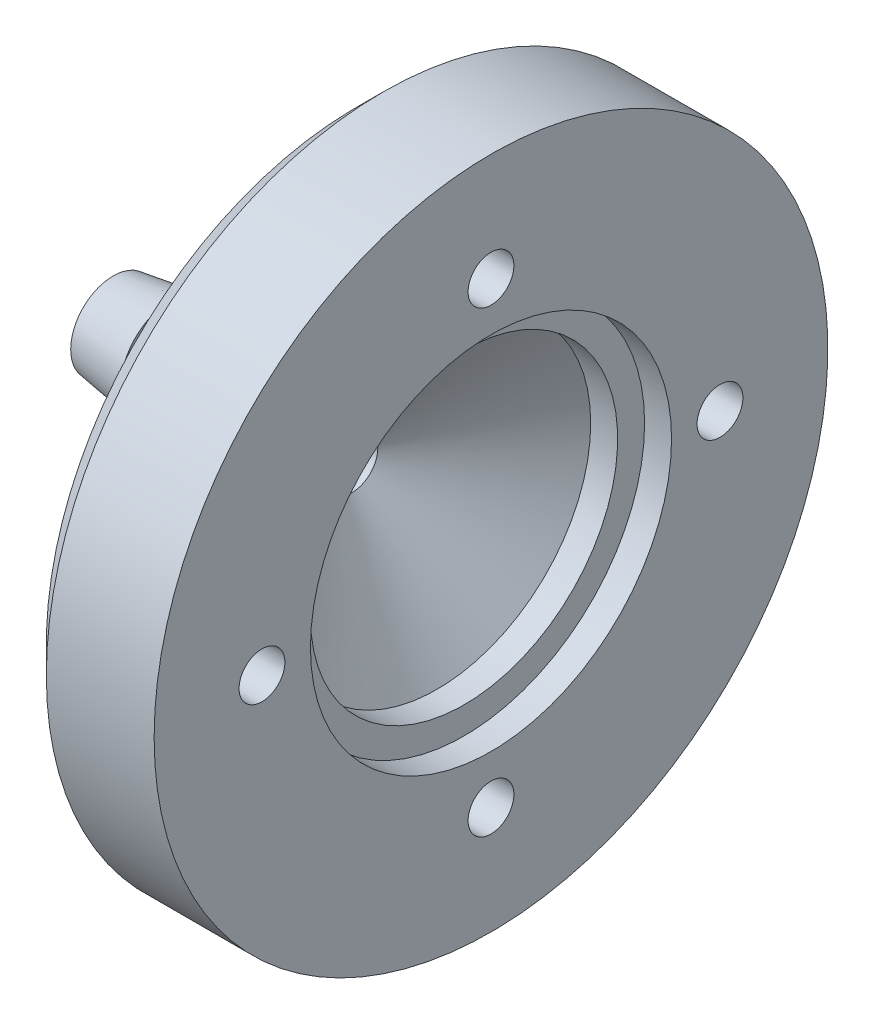
SolidWorks part; units mm, degrees
ref_plane "Front Plane" through (0, 0, 0) normal (0, 0, 1) x (1, 0, 0)
ref_plane "Top Plane" through (0, 0, 0) normal (0, 1, 0) x (1, 0, 0)
ref_plane "Right Plane" through (0, 0, 0) normal (1, 0, 0) x (0, 0, -1)
sketch "Sketch1" plane through (0, 0, 0) normal (0, 0, 1) x (1, 0, 0)
  line L0 (-801.9206, 0) -> (36107.5283, 0) construction
  line L3 (-13.4063, 3.8) -> (-13.4063, 3.15)
  line L8 (-17.7397, 1.9) -> (0, 1.9)
  line L9 (-17.7397, 1.9) -> (-17.7397, 3.15)
  line L10 (10.3016, 13.4) -> (10.3016, 25)
  line L12 (10.3016, 25) -> (0.3016, 25)
  line L16 (10.3016, 13.4) -> (8.3016, 13.4)
  line L17 (8.3016, 13.4) -> (8.3016, 11.4)
  line L18 (0.3016, 25) -> (0.3016, 11.4)
  line L20 (0, 1.9) -> (6.3016, 11.4)
  line L21 (-17.7397, 3.15) -> (-13.4063, 3.8)
  line L22 (6.3016, 11.4) -> (8.3016, 11.4)
  line L23 (-13.4063, 3.15) -> (-9.073, 3.8)
  line L25 (-9.073, 3.15) -> (-4.7397, 3.8)
  line L26 (-9.073, 3.8) -> (-9.073, 3.15)
  line L27 (-4.7397, 3.8) -> (0.3016, 11.4)
  dimension "D3" = 2
  dimension "D2" = 7.6
  dimension "D6" = 3.8
  dimension "D7" = 6.3
  dimension "D1" = 10
  dimension "D5" = 25
  dimension "D8" = 13.4
  dimension "D10" = 2
  dimension "D4" = 5
  dimension "D9" = 2
  dimension "D11" = 13
revolve "Revolve17" add sketch "Sketch1" angle 360 about L0
sketch "Sketch4" plane through (0.3016, 0, 0) normal (-1, 0, 0) x (0, 0, 1)
  circle A0 centre (0, 0) radius 16.9947 construction
  point P3 (0, 16.9947)
  point P7 (16.9947, 0)
  point P12 (-16.9947, 0)
  point P13 (0, -16.9947)
hole_wizard "M3 Clearance Hole1" positions "Sketch4" profile "Sketch5" hole size "M3" standard "ISO"
sketch "Sketch5" plane through (0.3016, -16.9947, 0) normal (0, 1, 0) x (0, 0, 1)
  line L0 (0, 0) -> (0, 11.0215)
  line L1 (0, 11.0215) -> (1.7, 10)
  line L2 (1.7, 10) -> (1.7, 0)
  line L5 (1.7, 0) -> (0, 0)
  line L10 (0, 11.0215) -> (-1.7, 10) construction
  line L11 (0, -6.35) -> (0, 107.95) construction
  dimension "Hole Dia." = 3.4
  dimension "Hole Depth" = 10
  dimension "Drill Angle" = 118
chamfer "Chamfer1" distance 2 angle 45 1 edges at (0.3016, 0, 25)
equation "\"D10@Sketch1\"=\"D3@Sketch1\""
equation "\"D9@Sketch1\"=\"D3@Sketch1\""
